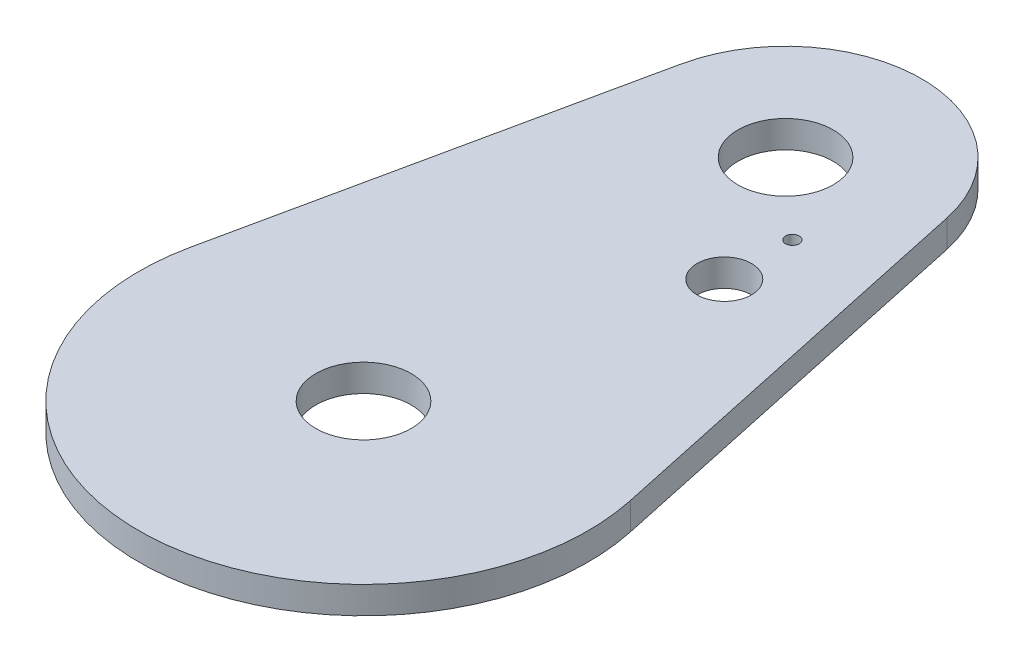
SolidWorks part; units mm, degrees
ref_plane "Piano frontale" through (0, 0, 0) normal (0, 0, 1) x (1, 0, 0)
ref_plane "Piano superiore" through (0, 0, 0) normal (0, 1, 0) x (1, 0, 0)
ref_plane "Piano destro" through (0, 0, 0) normal (1, 0, 0) x (0, 0, -1)
sketch "Schizzo1" plane through (0, 0, 0) normal (0, 1, 0) x (1, 0, 0)
  line L0 (0, -58.8657) -> (0, 82) construction
  line L1 (-19.5554, 66.1935) -> (-32.2664, 6.9194)
  line L2 (19.5554, 66.1935) -> (32.2664, 6.9194)
  circle A0 centre (0, 62) radius 7
  circle A1 centre (0, 0) radius 7
  arc A2 (19.5554, 66.1935) -> (-19.5554, 66.1935) centre (0, 62) ccw
  arc A3 (-32.2664, 6.9194) -> (32.2664, 6.9194) centre (0, 0) ccw
  circle A4 centre (11, 52) radius 1
  circle A5 centre (11, 42) radius 4
  point P14 (0, 0)
  dimension "D1" = 14
  dimension "D2" = 62
  dimension "D3" = 66
  dimension "D4" = 40
  dimension "D5" = 2
  dimension "D8" = 8
  dimension "D6" = 10
  dimension "D7" = 11
  dimension "D9" = 20
base flange "Base-Flangia1" sketch "Schizzo1" thickness 4 reverse thickness direction no parameters "D1"=0.7366
sketch "Linee di piegatura1" [suppressed] plane through (0, 0, 0) normal (0, 1, 0) x (1, 0, 0)
sketch "Casella di contorno1" [suppressed] plane through (0, 0, 0) normal (0, 1, 0) x (1, 0, 0)
sheet metal parameters "Lamiera1" thickness 4 parameters "D1"=0.7366
flat pattern "Ripetizione piatta1" [suppressed]
sketch "Linee di piegatura2" plane through (0, 0, 0) normal (0, 1, 0) x (1, 0, 0)
sketch3d "Casella di contorno2" [suppressed]
  line L0 (49.171, 9.9102, 0) -> (25.3471, -101.1858, 0) construction
  line L1 (-15.3619, 23.7489, 0) -> (-39.1858, -87.3471, 0) construction
  line L2 (49.171, 9.9102, 0) -> (-15.3619, 23.7489, 0) construction
  line L3 (25.3471, -101.1858, 0) -> (-39.1858, -87.3471, 0) construction
